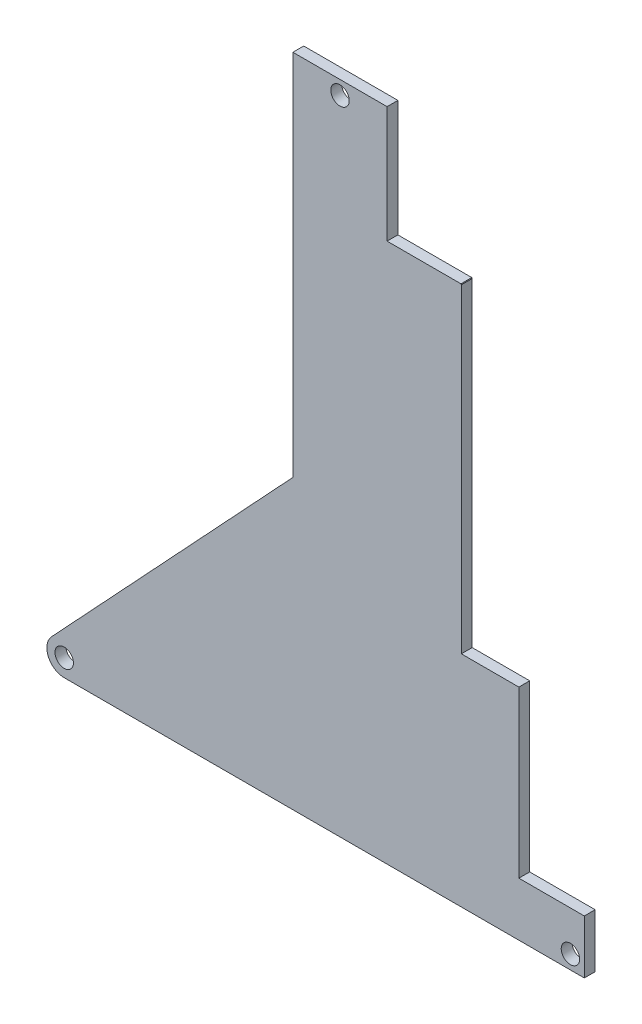
SolidWorks part; units mm, degrees
ref_plane "Front Plane" through (0, 0, 0) normal (0, 0, 1) x (1, 0, 0)
ref_plane "Top Plane" through (0, 0, 0) normal (0, 1, 0) x (1, 0, 0)
ref_plane "Right Plane" through (0, 0, 0) normal (1, 0, 0) x (0, 0, -1)
sketch "Sketch1" plane through (0, 0, 0) normal (0, 0, 1) x (1, 0, 0)
  line L1 (-52.6486, -67.2724) -> (-30.5784, -43.6209)
  line L3 (-30.5784, -43.6209) -> (-18.8373, -31.0385)
  line L4 (-18.8373, 22.9178) -> (-18.8373, 15.0967)
  line L5 (-62.4049, -73.074) -> (-22.4391, -30.2446) construction
  line L6 (-54.2124, -68.9483) -> (-52.6486, -67.2724)
  line L7 (-60.0836, -75.2401) -> (-20.1178, -32.4107) construction
  line L9 (23.8665, -73.2212) -> (-30.5784, -73.2212)
  line L12 (-18.8373, 15.0967) -> (-18.8373, -31.0385)
  line L13 (-30.5784, -73.2212) -> (-52.3554, -73.2212)
  line L14 (-18.8373, 22.9178) -> (-5.0365, 22.9178)
  line L20 (23.8665, -65.3472) -> (23.8665, -73.2212)
  arc A1 (25.454, -65.3472) -> (-3.6178, 23.6674) centre (-125.3585, -65.3472) ccw construction
  arc A2 (23.8665, -65.3472) -> (-5.0365, 22.9178) centre (-125.3585, -65.3472) ccw
  arc A3 (23.8665, -65.3472) -> (-4.8993, 22.7304) centre (-125.3585, -65.3472) ccw construction
  arc A7 (-52.3554, -73.2212) -> (-54.2124, -68.9483) centre (-52.3554, -70.6812) cw
  dimension "D5" = 2.54
  dimension "D1" = 1.5875
  dimension "D2" = 3.175
extrude "Boss-Extrude1" add sketch "Sketch1" along normal blind 1.5875
hole_wizard "#2 Clearance Hole1" positions "Sketch3" profile "Sketch2" hole size "#2" standard "ANSI Inch" end condition through all
sketch "Sketch3" plane through (0, 0, 0) normal (0, 0, -1) x (-1, 0, 0)
  line L0 (11.9369, 20.8858) -> (11.9369, 22.9178) construction
  line L1 (5.0365, 22.9178) -> (18.8373, 22.9178) construction
  line L2 (-23.8665, -73.2212) -> (-23.8665, -65.3472) construction
  line L3 (52.3554, -73.2212) -> (-23.8665, -73.2212) construction
  point P0 (-21.8345, -71.1892)
  point P2 (52.3554, -70.6812)
  point P5 (11.9369, 20.8858)
  dimension "D1" = 2.032
  dimension "D2" = 2.032
  dimension "D3" = 2.032
sketch "Sketch2" plane through (21.8345, -71.1892, 0) normal (1, 0, 0) x (0, 1, 0)
  line L0 (0, 0) -> (0, 1.5875)
  line L1 (0, 1.5875) -> (1.3525, 1.5875)
  line L2 (1.3525, 1.5875) -> (1.3525, 0)
  line L5 (1.3525, 0) -> (0, 0)
  line L11 (0, -6.35) -> (0, 107.95) construction
  dimension "Thru Hole Dia." = 2.7051
  dimension "Thru Hole Depth" = 1.5875
sketch "Sketch4" plane through (0, 0, 0) normal (0, 0, -1) x (-1, 0, 0)
  line L1 (-23.8665, -65.3472) -> (-14.278, -65.3472)
  line L2 (-23.8665, -65.3472) -> (-23.8665, -41.0902)
  line L3 (-23.8665, -41.0902) -> (-14.278, -41.0902)
  line L4 (-14.278, -65.3472) -> (-14.278, -41.0902)
  line L5 (-23.8665, -65.3472) -> (-14.278, -41.0902) construction
  line L6 (-23.8665, -41.0902) -> (-14.278, -65.3472) construction
  line L8 (-14.278, -41.0902) -> (-9.1472, -41.0902) construction
  line L9 (-14.278, -73.9832) -> (-14.278, -41.0902) construction
  line L10 (-5.8452, 5.8452) -> (-21.8817, 5.8452)
  line L11 (-5.8452, 5.8452) -> (-5.8452, -41.0902)
  line L12 (-5.8452, -41.0902) -> (-21.8817, -41.0902)
  line L13 (-21.8817, 5.8452) -> (-21.8817, -41.0902)
  line L14 (-5.8452, 5.8452) -> (-21.8817, -41.0902) construction
  line L15 (-5.8452, -41.0902) -> (-21.8817, 5.8452) construction
  line L16 (5.0365, 22.9178) -> (-5.8452, 22.9178)
  line L17 (5.0365, 22.9178) -> (5.0365, 5.8452)
  line L18 (5.0365, 5.8452) -> (-5.8452, 5.8452)
  line L19 (-5.8452, 22.9178) -> (-5.8452, 5.8452)
  line L20 (5.0365, 22.9178) -> (-5.8452, 5.8452) construction
  line L21 (5.0365, 5.8452) -> (-5.8452, 22.9178) construction
  arc A0 (5.0365, 22.9178) -> (-23.8665, -65.3472) centre (125.3585, -65.3472) ccw construction
  point P4 (-19.0722, -53.2187)
  point P14 (-13.8635, -17.6225)
  point P23 (-0.4043, 14.3815)
  arc M8 (5.0365, 22.9178) -> (-23.8665, -65.3472) centre (125.3585, -65.3472) ccw
extrude "Cut-Extrude1" cut sketch "Sketch4" against normal through all contours L1 L4 L3 M8 | L12 L11 L3 M8 | L18 L17 M8 region at (18.7619, -53.6674, 0) region at (11.7225, -24.2369, 0) region at (-1.3365, 11.675, 0)
sketch "Sketch5" plane through (0, 0, 1.5875) normal (0, 0, 1) x (1, 0, 0)
  line L0 (23.8665, -73.2212) -> (23.8665, -65.3472) construction
  line L1 (-52.3554, -73.2212) -> (23.8665, -73.2212) construction
  line L2 (-18.8373, -31.0385) -> (-54.2124, -68.9483) construction
  line L3 (-18.8373, 22.9178) -> (-18.8373, -31.0385) construction
  line L4 (-5.0365, 22.9178) -> (-18.8373, 22.9178) construction
  line L5 (23.8665, -73.2212) -> (23.8665, -65.3472)
  line L6 (-52.3554, -73.2212) -> (23.8665, -73.2212)
  line L7 (-18.8373, -31.0385) -> (-54.2124, -68.9483)
  line L8 (-18.8373, 22.9178) -> (-18.8373, -31.0385)
  line L9 (-5.0365, 22.9178) -> (-18.8373, 22.9178)
  arc A1 (-54.2124, -68.9483) -> (-52.3554, -73.2212) centre (-52.3554, -70.6812) ccw construction
  arc A2 (23.8665, -65.3472) -> (-4.8993, 22.7304) centre (-125.3585, -65.3472) ccw
  arc A3 (23.8665, -65.3472) -> (-4.8993, 22.7304) centre (-125.3585, -65.3472) ccw
  arc A4 (-54.2124, -68.9483) -> (-52.3554, -73.2212) centre (-52.3554, -70.6812) ccw
  circle A5 centre (-11.9369, 20.8858) radius 1.3525 construction
  circle A6 centre (-11.9369, 20.8858) radius 1.3525
  circle A7 centre (-52.3554, -70.6812) radius 1.3526 construction
  circle A8 centre (21.8345, -71.1892) radius 1.3525 construction
  circle A9 centre (-52.3554, -70.6812) radius 1.3526
  circle A10 centre (21.8345, -71.1892) radius 1.3526
  circle A11 centre (-8.1059, -0.0354) radius 0.5
  circle A12 centre (-0.0354, 0.0351) radius 0.5
  circle A13 centre (0.0351, -8.0355) radius 0.5
  circle A14 centre (-8.0355, -8.1059) radius 0.5
  circle A15 centre (-0.0354, -23.9387) radius 0.5
  circle A16 centre (-8.1059, -24.0091) radius 0.5
  circle A17 centre (-8.0355, -32.0797) radius 0.5
  circle A18 centre (0.0351, -32.0092) radius 0.5
  circle A19 centre (9.452, -44.697) radius 0.5
  circle A20 centre (0.4604, -44.697) radius 0.5
  circle A21 centre (-8.5312, -44.697) radius 0.5
  circle A22 centre (-17.5228, -44.697) radius 0.5
  circle A23 centre (-26.5144, -44.697) radius 0.5
  circle A24 centre (9.452, -53.2314) radius 0.5
  circle A25 centre (0.4604, -53.2314) radius 0.5
  circle A26 centre (-8.5312, -53.2314) radius 0.5
  circle A27 centre (-17.5228, -53.2314) radius 0.5
  circle A28 centre (-26.5144, -53.2314) radius 0.5
  circle A29 centre (-35.506, -61.842) radius 0.5
  circle A30 centre (-26.5144, -61.842) radius 0.5
  circle A31 centre (-17.5228, -61.842) radius 0.5
  circle A32 centre (-8.5312, -61.842) radius 0.5
  circle A33 centre (0.4604, -61.842) radius 0.5
  circle A34 centre (9.452, -61.842) radius 0.5
  circle A35 centre (9.452, -70.3764) radius 0.5
  circle A36 centre (0.4604, -70.3764) radius 0.5
  circle A37 centre (-8.5312, -70.3764) radius 0.5
  circle A38 centre (-17.5228, -70.3764) radius 0.5
  circle A39 centre (-26.5144, -70.3764) radius 0.5
  circle A40 centre (-35.506, -70.3764) radius 0.5
  circle A41 centre (-4.0354, -4.0354) radius 2.54
  circle A42 centre (-4.0354, -28.0092) radius 2.54
  dimension "D2" = 1
  dimension "D3" = 5.08
  dimension "D1" = 1.5875
